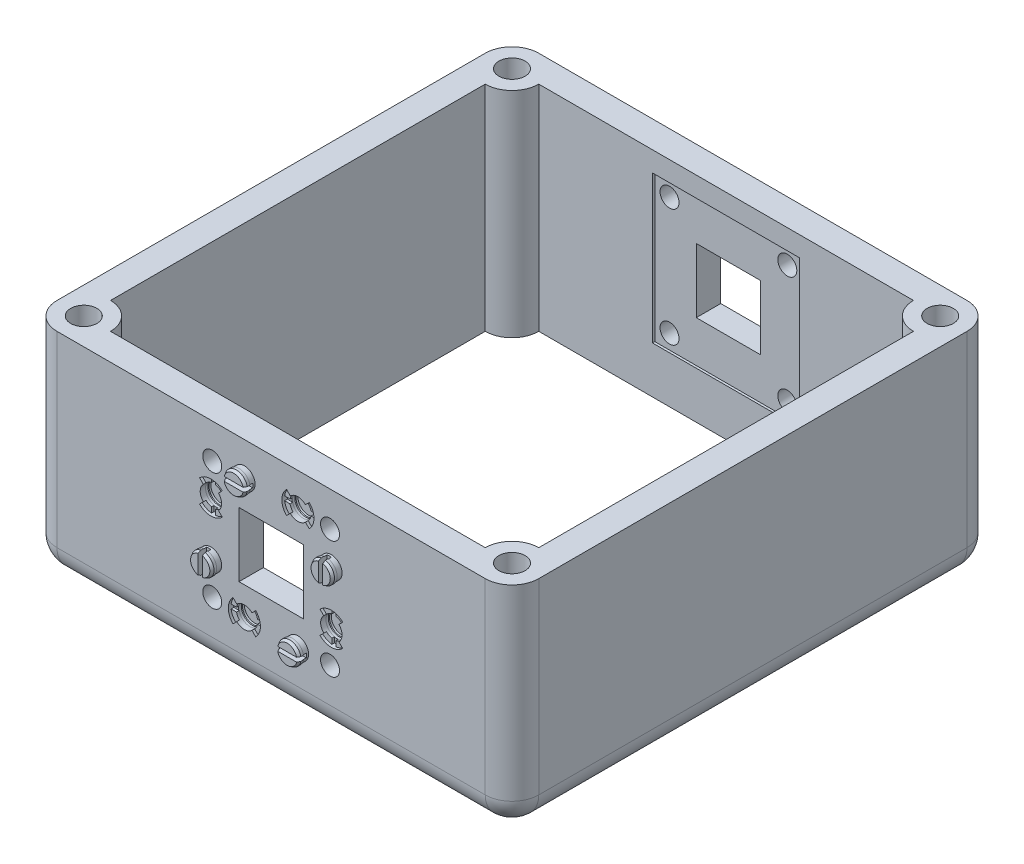
SolidWorks part; units mm, degrees
note: '?' marks a value the reader was unsure of. The reader was unsure of these and kept them because the rebuilt part matched: shared geometry of "Sketch5<3>", "Sketch13<4>", "Sketch13<5>", "Sketch13<6>".
ref_plane "Front Plane" through (0, 0, 0) normal (0, 0, 1) x (1, 0, 0)
ref_plane "Top Plane" through (0, 0, 0) normal (0, 1, 0) x (1, 0, 0)
ref_plane "Right Plane" through (0, 0, 0) normal (1, 0, 0) x (0, 0, -1)
sketch "Sketch1" plane through (0, 0, 0) normal (0, 1, 0) x (1, 0, 0)
  line L1 (-57.15, 57.15) -> (57.15, 57.15)
  line L2 (-57.15, 57.15) -> (-57.15, -57.15)
  line L3 (-57.15, -57.15) -> (57.15, -57.15)
  line L4 (57.15, 57.15) -> (57.15, -57.15)
  point P4 (0, 57.15)
  point P7 (-57.15, 0)
  dimension "D1" = 114.3
  dimension "D2" = 114.3
extrude "Boss-Extrude1" add sketch "Sketch1" along normal mid plane 50.8
sketch "Sketch2" plane through (0, 25.4, 0) normal (0, 1, 0) x (1, 0, 0)
  line L1 (-50.8, 50.8) -> (50.8, 50.8)
  line L2 (-50.8, 50.8) -> (-50.8, -50.8)
  line L3 (-50.8, -50.8) -> (50.8, -50.8)
  line L4 (50.8, 50.8) -> (50.8, -50.8)
  arc A0 (-50.8, 44.45) -> (-44.45, 50.8) centre (-50.8, 50.8) ccw
  arc A1 (44.45, 50.8) -> (50.8, 44.45) centre (50.8, 50.8) ccw
  arc A2 (-50.8, -44.45) -> (-44.45, -50.8) centre (-50.8, -50.8) cw
  arc A3 (44.45, -50.8) -> (50.8, -44.45) centre (50.8, -50.8) cw
  point P4 (0, 50.8)
  point P5 (50.8, 0)
  dimension "D3" = 6.35
  dimension "D4" = 6.35
  dimension "D5" = 6.35
  dimension "D6" = 6.35
  dimension "D1" = 101.6
  dimension "D2" = 101.6
extrude "Cut-Extrude1" cut sketch "Sketch2" against normal blind 50.8 contours L3 A3 L4 A1 L1 A0 L2 A2
hole_wizard "CBORE for #0 Binding Head Machine Screw1" positions "3DSketch2" profile "Sketch4" counterbore size "#0" standard "ANSI Inch"
sketch3d "3DSketch2"
  point P0 (-50.8, 25.4, -50.8)
  point P3 (50.8, 25.4, -50.8)
  point P6 (-50.8, 25.4, 50.8)
  point P9 (50.8, 25.4, 50.8)
sketch "Sketch4" plane through (-50.8, 25.4, -50.8) normal (1, 0, 0) x (0, 0, 1)
  line L0 (0, 0) -> (0, 18.288)
  line L1 (0, 18.288) -> (0.9271, 17.7309)
  line L2 (0.9271, 17.7309) -> (0.9271, 9.144)
  line L3 (0.9271, 9.144) -> (3.1115, 9.144)
  line L4 (3.1115, 9.144) -> (3.1115, 0)
  line L5 (3.1115, 0) -> (0, 0)
  line L10 (0, 18.288) -> (-0.9271, 17.7309) construction
  line L11 (0, -6.35) -> (0, 107.95) construction
  dimension "Hole Dia." = 1.8542
  dimension "Hole Depth" = 18.288
  dimension "C'Bore Dia." = 6.223
  dimension "C'Bore Depth" = 9.144
  dimension "Drill Angle" = 118
sketch "Sketch5" plane through (0, 0, -50.8) normal (0, 0, 1) x (1, 0, 0)
  line L0 (7.625, 3.175) -> (-7.625, 3.175) construction
  line L1 (-17.47, 20.645) -> (17.47, 20.645)
  line L2 (-17.47, 20.645) -> (-17.47, -14.295)
  line L3 (-17.47, -14.295) -> (17.47, -14.295)
  line L4 (17.47, 20.645) -> (17.47, -14.295)
  line L5 (-7.625, 10.8) -> (7.625, 10.8)
  line L6 (-7.625, 10.8) -> (-7.625, -4.45)
  line L7 (-7.625, -4.45) -> (7.625, -4.45)
  line L8 (7.625, 10.8) -> (7.625, -4.45)
  line L10 (-57.15, 25.4) -> (-57.15, -25.4) construction
  line L11 (0, 10.8) -> (0, -4.45) construction
  line L12 (-57.15, 25.4) -> (57.15, 25.4) construction
  point P8 (0, 10.8)
  point P9 (0, 20.645)
  point P12 (17.47, 3.175)
  point P13 (7.625, 3.175)
  dimension "D1" = 34.94
  dimension "D2" = 15.25
  dimension "D3" = 15.25
  dimension "D4" = 34.94
  dimension "D5" = 39.68
  dimension "D6" = 4.755
extrude "Cut-Extrude5" cut sketch "Sketch5" against normal blind 0.55
extrude "Cut-Extrude6" cut sketch "Sketch5<3>" against normal up to next
sketch "Sketch5<3>" plane through (0, 0, -50.8) normal (0, 0, 1) x (1, 0, 0) same geometry as "Sketch5"
sketch "Sketch13" plane through (0, 0, -57.15) normal (0, 0, -1) x (-1, 0, 0)
  line L0 (-57.15, 25.4) -> (57.15, 25.4) construction
  line L1 (-57.15, 25.4) -> (-57.15, -25.4) construction
  line L2 (57.15, 25.4) -> (57.15, -25.4) construction
  line L3 (-14.2875, -0.635) -> (-14.2875, -5.715) construction
  line L4 (14.2875, -5.715) -> (14.2875, -0.635) construction
  line L5 (13.7875, 0.602) -> (13.7875, -6.952)
  line L6 (14.7875, 0.602) -> (14.7875, -6.952)
  line L7 (11.5934, -5.8691) -> (16.9816, -0.4809)
  line L8 (11.5934, -0.4809) -> (16.9816, -5.8691)
  circle A0 centre (-14.2875, -3.175) radius 2.54
  circle A1 centre (14.2875, -3.175) radius 2.54
  circle A2 centre (14.2875, -3.175) radius 3.81
  point P19 (13.7875, -3.175)
  point P20 (14.7875, -3.175)
  dimension "D1" = 5.08
  dimension "D2" = 5.08
  dimension "D7" = 7.62
  dimension "D3" = 28.575
  dimension "D4" = 28.575
  dimension "D5" = 42.8625
  dimension "D6" = 42.8625
  dimension "D8" = 1
  dimension "D9" = 0.5
  dimension "D10" = 45
  dimension "D11" = 45
extrude "Boss-Extrude2" add sketch "Sketch13" along normal blind 1.27 contours A0
ref_plane "Plane1" through (14.2875, -3.175, -57.15) normal (0, -1, 0) x (-1, 0, 0)
sketch "Sketch14" plane through (14.2875, -3.175, -57.15) normal (0, -1, 0) x (-1, 0, 0)
  line L0 (0, 1.27) -> (0, 2.54)
  line L1 (2.54, 1.27) -> (-2.54, 1.27) construction
  line L2 (0, 2.54) -> (2.286, 2.54)
  line L3 (2.286, 2.54) -> (2.64, 1.905)
  line L4 (2.64, 1.905) -> (2.64, 1.27)
  line L5 (2.64, 1.27) -> (2.54, 1.27)
  line L6 (2.54, 0) -> (2.54, 1.27) construction
  line L7 (2.54, 1.27) -> (0, 1.27)
  dimension "D1" = 1.27
  dimension "D2" = 0.1
  dimension "D3" = 2.286
  dimension "D4" = 0.635
revolve "Revolve1" add sketch "Sketch14" angle 360 about L0
ref_plane "Plane2" through (-14.2875, -3.175, -57.15) normal (0, -1, 0) x (-1, 0, 0)
extrude "Cut-Extrude7" cut sketch "Sketch13<4>" against normal blind 2.54 contours L8 A1 L7 L6 | L6 A1 L8 | L5 A1 L6 L8 L7 | L7 A1 L6 | L6 A1 L5 L8 L7 | L7 L8 L6 | L8 L5 L7 | L8 A1 L7 L5 | L7 A1 L5 | L5 A1 L8
sketch "Sketch13<4>" plane through (0, 0, -57.15) normal (0, 0, -1) x (-1, 0, 0) same geometry as "Sketch13"
extrude "Cut-Extrude8" cut sketch "Sketch13<5>" against normal blind 0.635 contours L7 A2 L5 A1 | L6 A2 L8 A1 | L7 A2 L6 A1 | L5 A2 L8 A1
sketch "Sketch13<5>" plane through (0, 0, -57.15) normal (0, 0, -1) x (-1, 0, 0) same geometry as "Sketch13"
extrude "Cut-Extrude9" cut sketch "Sketch13<6>" against normal blind 1.27 contours L6 A2 L5 A1 | L5 A2 L6 A1
sketch "Sketch13<6>" plane through (0, 0, -57.15) normal (0, 0, -1) x (-1, 0, 0) same geometry as "Sketch13"
sketch "Sketch17" plane through (-14.2875, -3.175, -57.15) normal (0, -1, 0) x (-1, 0, 0)
  line L0 (0, -1.27) -> (0, -2.54)
  line L1 (0.5, -1.27) -> (-0.5, -1.27) construction
  line L2 (0, -2.54) -> (2.286, -2.54)
  line L3 (2.286, -2.54) -> (2.64, -1.905)
  line L7 (2.54, -1.27) -> (0, -1.27)
  line L8 (2.64, -1.905) -> (2.64, -1.27)
  line L9 (2.64, -1.27) -> (2.54, -1.27)
  dimension "D1" = 2.54
  dimension "D2" = 2.286
  dimension "D3" = 0.1
  dimension "D4" = 1.27
  dimension "D5" = 0.635
revolve "Cut-Revolve1" cut sketch "Sketch17" angle 360 about L0
ref_plane "Plane3" through (0, 3.175, 0) normal (0, -1, 0) x (0, 0, 1)
ref_axis "Axis1" through (0, 3.175, 62.865) along (0, 0, -1)?
ref_axis "Axis2" through (0, 59.3725, 0) along (0, -1, 0)?
sketch "Sketch20" plane through (0, 0, -57.15) normal (0, 0, -1) x (-1, 0, 0)
  line L1 (-13.97, 17.145) -> (13.97, 17.145)
  line L2 (-13.97, 17.145) -> (-13.97, -10.795)
  line L3 (-13.97, -10.795) -> (13.97, -10.795)
  line L4 (13.97, 17.145) -> (13.97, -10.795)
  point P4 (0, 17.145)
  point P9 (13.97, 3.175)
  dimension "D1" = 27.94
  dimension "D2" = 27.94
hole_wizard "CBORE for M5 Hex Head Bolt2" positions "3DSketch4" profile "Sketch21" counterbore size "M5" standard "ANSI Metric"
sketch3d "3DSketch4"
  point P0 (13.97, 17.145, -57.15)
  point P3 (-13.97, 17.145, -57.15)
  point P6 (-13.97, -10.795, -57.15)
  point P9 (13.97, -10.795, -57.15)
sketch "Sketch21" plane through (13.97, 17.145, -57.15) normal (1, 0, 0) x (0, 1, 0)
  line L0 (0, 0) -> (0, 18.288)
  line L1 (0, 18.288) -> (2.75, 16.6356)
  line L2 (2.75, 16.6356) -> (2.75, 5.8)
  line L3 (2.75, 5.8) -> (2.25, 5.8)
  line L4 (2.25, 5.8) -> (2.25, 0)
  line L5 (2.25, 0) -> (0, 0)
  line L10 (0, 18.288) -> (-2.75, 16.6356) construction
  line L11 (0, -6.35) -> (0, 107.95) construction
  dimension "Hole Dia." = 5.5
  dimension "Hole Depth" = 18.288
  dimension "C'Bore Dia." = 4.5
  dimension "C'Bore Depth" = 5.8
  dimension "Drill Angle" = 118
sketch "Sketch23" plane through (0, 0, -59.69) normal (0, 0, -1) x (-1, 0, 0)
  line L0 (-14.7875, -0.5828) -> (-14.7875, -5.7672)
  line L1 (-13.7875, -0.5828) -> (-13.7875, -5.7672)
  line L2 (-14.2875, -0.535) -> (-14.2875, -5.815) construction
  circle A0 centre (-14.2875, -3.175) radius 2.64 construction
  circle A1 centre (-14.2875, -3.175) radius 2.64
  circle M1 centre (-14.2875, -3.175) radius 2.286
  dimension "D1" = 5.28
  dimension "D2" = 0.5
  dimension "D3" = 0.5
extrude "Cut-Extrude10" cut sketch "Sketch23" against normal blind 2.032 contours L2 L0 M1 | L2 L1 M1 | L2 A1 L0 M1 | A1 L2 L1 M1 | L2 A1 L1 M1 | L2 L0 A1 M1
pattern_circular "CirPattern1" count 4 every 90 about axis through (0, 3.175, 0) along (0, 0, 1) of "Boss-Extrude2", "Revolve1", "Cut-Extrude7", "Cut-Extrude8", "Cut-Extrude9", "Cut-Revolve1", "Cut-Extrude10"
ref_plane "Plane4" through (0, 3.175, 0) normal (0, -1, 0) x (-1, 0, 0)
ref_axis "Axis3" through (-62.865, 3.175, 0) along (1, 0, 0)
pattern_circular "CirPattern2" count 2 over 180 about axis through (0, 3.175, 0) along (1, 0, 0) of "CirPattern1", "Boss-Extrude2", "Revolve1", "Cut-Extrude7", "Cut-Extrude8", "Cut-Extrude9", "Cut-Revolve1", "Cut-Extrude10"
pattern_circular "CirPattern3" count 2 over 180 about axis through (0, 3.175, 0) along (1, 0, 0) of "Cut-Extrude5", "Cut-Extrude6", "CBORE for M5 Hex Head Bolt2"
fillet "Fillet1" radius 6.35 8 edges at (0, -25.4, -57.15) (57.15, -25.4, 0) (0, -25.4, 57.15) (-57.15, -25.4, 0) (-57.15, 0, 57.15) (-57.15, 0, -57.15) (57.15, 0, 57.15) (57.15, 0, -57.15)
